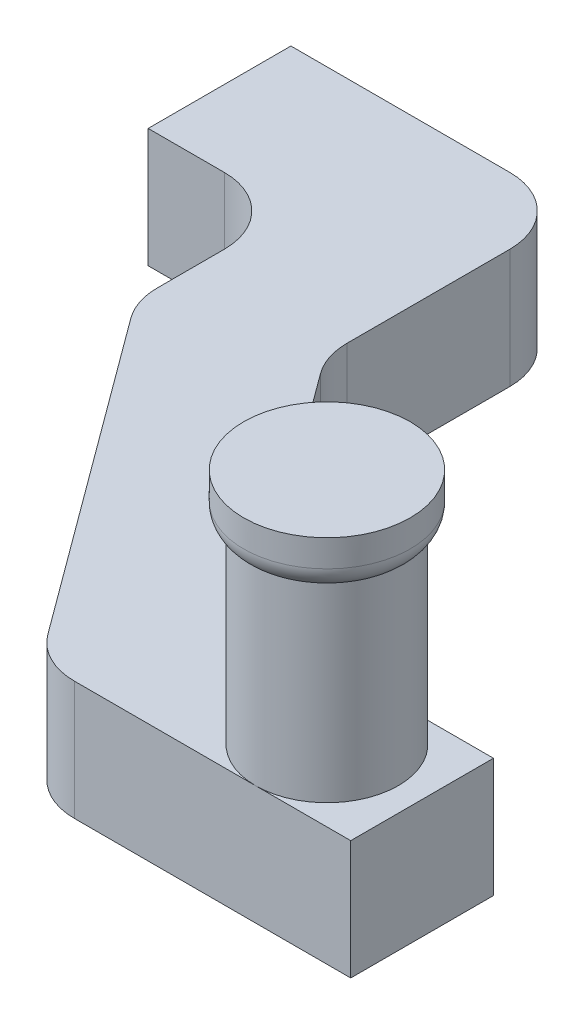
SolidWorks part; units mm, degrees
ref_plane "Front Plane" through (0, 0, 0) normal (0, 0, 1) x (1, 0, 0)
ref_plane "Top Plane" through (0, 0, 0) normal (0, 1, 0) x (1, 0, 0)
ref_plane "Right Plane" through (0, 0, 0) normal (1, 0, 0) x (0, 0, -1)
sketch "Sketch1" plane through (0, 0, 0) normal (0, 1, 0) x (1, 0, 0)
  line L0 (0, 0) -> (6, 0)
  line L1 (6, 0) -> (6, -5.2806)
  line L2 (6, -5.2806) -> (10.0922, -10.8346)
  line L3 (10.0922, -10.8346) -> (15.0922, -10.8346)
  line L4 (0, -3) -> (3, -3)
  line L5 (3, -3) -> (3, -6.2665)
  line L6 (3, -6.2665) -> (8.5763, -13.8346)
  line L7 (8.5763, -13.8346) -> (15.0922, -13.8346)
  line L8 (15.0922, -10.8346) -> (15.0922, -13.8346)
  line L9 (0, 0) -> (0, -3)
  dimension "D1" = 6
  dimension "D4" = 5
  dimension "D5" = 3
extrude "Boss-Extrude1" add sketch "Sketch1" along normal blind 2.5
fillet "Fillet1" radius 1.4 5 edges at (6, 1.25, 5.2806) (3, 1.25, 6.2665) (3, 1.25, 3) (6, 1.25, 0) (8.5763, 1.25, 13.8346)
sketch "Sketch2" plane through (0, 2.5, 0) normal (0, 1, 0) x (1, 0, 0)
  line L0 (15.0922, -10.8346) -> (10.0922, -10.8346) construction
  line L1 (15.0922, -13.8346) -> (15.0922, -10.8346) construction
  circle A0 centre (13.0922, -12.3346) radius 1.5
  dimension "D1" = 1.5
  dimension "D2" = 2
extrude "Boss-Extrude2" add sketch "Sketch2" along normal blind 4
sketch "Sketch3" plane through (0, 6.5, 0) normal (0, 1, 0) x (1, 0, 0)
  circle A0 centre (13.0922, -12.3346) radius 1.75
extrude "Boss-Extrude3" add sketch "Sketch3" along normal blind 1
fillet "Fillet2" radius 0.5 1 edges at (13.0922, 6.5, 14.0846)
sketch "Sketch4" plane through (0, 0, 0) normal (0, -1, 0) x (-1, 0, 0)
  circle A0 centre (-1.718, -1.4929) radius 1.4
extrude "Boss-Extrude4" add sketch "Sketch4" along normal blind 3.5
sketch "Sketch5" plane through (0, -3.5, 0) normal (0, -1, 0) x (1, 0, 0)
  circle A0 centre (1.7071, 1.4764) radius 1.7
extrude "Boss-Extrude5" add sketch "Sketch5" along normal blind 1
fillet "Fillet3" radius 0.5 1 edges at (1.7071, -3.5, -0.2236)
